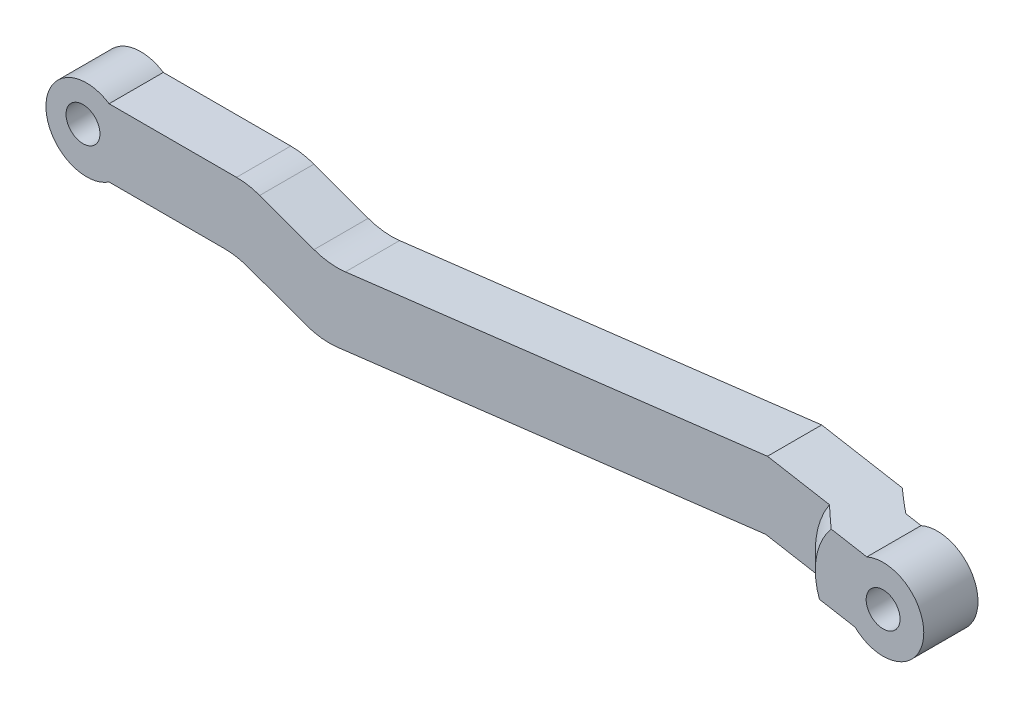
SolidWorks part; units mm, degrees
material "Vero PureWhite"
ref_plane "前视基准面" through (0, 0, 0) normal (0, 0, 1) x (1, 0, 0)
ref_plane "上视基准面" through (0, 0, 0) normal (0, 1, 0) x (1, 0, 0)
ref_plane "右视基准面" through (0, 0, 0) normal (1, 0, 0) x (0, 0, -1)
other "Configuration Table"
sketch "草图1" plane through (0, 0, 0) normal (0, 0, 1) x (1, 0, 0)
  line L0 (0, 0) -> (-120, 0) construction
  line L3 (0, 0) -> (-19.6962, 3.473) construction
  line L4 (-19.6962, 3.473) -> (-84.784, -4.4463) construction
  line L5 (-84.784, -4.4463) -> (-97, 0) construction
  line L6 (-97, 0) -> (-120, 0) construction
  line L7 (-2.398, 5.5) -> (-19.5611, 8.5263)
  line L8 (-19.5611, 8.5263) -> (-84.1992, 0.6618)
  line L9 (-84.1992, 0.6618) -> (-96.1184, 5)
  line L10 (-96.1184, 5) -> (-116.6834, 5)
  line L11 (-4.1345, -4.3481) -> (-19.8313, -1.5803)
  line L12 (-19.8313, -1.5803) -> (-85.3688, -9.5543)
  line L13 (-85.3688, -9.5543) -> (-97.8816, -5)
  line L14 (-97.8816, -5) -> (-116.6834, -5)
  line L15 (0.8682, 4.924) -> (-19.5611, 8.5263) construction
  line L16 (-0.8682, -4.924) -> (-19.8313, -1.5803) construction
  line L17 (-96.1184, 5) -> (-120, 5) construction
  line L18 (-97.8816, -5) -> (-120, -5) construction
  arc A0 (-4.1345, -4.3481) -> (-2.398, 5.5) centre (0, 0) ccw
  arc A1 (-116.6834, 5) -> (-116.6834, -5) centre (-120, 0) ccw
  arc A2 (-0.7041, 5.9585) -> (1.0949, -5.8993) centre (0, 0) ccw construction
  point P3 (-60, 0)
  dimension "D2" = 20
  dimension "D1" = 120
  dimension "D3" = 23
  dimension "D4" = 13
  dimension "D5" = 20
  dimension "D6" = 10
  dimension "D7" = 5
  dimension "D8" = 5
extrude "凸台-拉伸1" add sketch "草图1" along normal mid plane 8
sketch "草图2" plane through (0, 0, -4) normal (0, 0, -1) x (-1, 0, 0)
  circle A0 centre (0, 0) radius 10
  dimension "D1" = 20
extrude "切除-拉伸1" cut sketch "草图2" against normal blind 2.5
sketch "草图3" plane through (0, 0, 4) normal (0, 0, 1) x (1, 0, 0)
  line L2 (-2.398, 5.5) -> (-7.6604, 6.4279)
  line L3 (-9.3969, -3.4202) -> (-4.1345, -4.3481)
  line L4 (-2.398, 5.5) -> (-7.6604, 6.4279)
  line L5 (-9.3969, -3.4202) -> (-4.1345, -4.3481)
  arc A2 (-4.1345, -4.3481) -> (-2.398, 5.5) centre (0, 0) ccw
  arc A3 (-7.6604, 6.4279) -> (-9.3969, -3.4202) centre (0, 0) ccw
  arc A4 (-4.1345, -4.3481) -> (-2.398, 5.5) centre (0, 0) ccw
  arc A5 (-7.6604, 6.4279) -> (-9.3969, -3.4202) centre (0, 0) ccw
  dimension "D1" = 0
extrude "凸台-拉伸4" add sketch "草图3" along normal offset from surface (2.5 mm away) 8 up to face at (-3.9335, 0.6936, -1.5)
sketch "草图4" plane through (0, 0, -1.5) normal (0, 0, -1) x (-1, 0, 0)
  circle A2 centre (0, 0) radius 2.5
  circle A3 centre (120.5349, 0.4793) radius 2.5003
  dimension "D1" = 5
  dimension "D2" = 5.0006
extrude "切除-拉伸2" cut sketch "草图4" against normal through all both and the other way through all
chamfer "倒角1" distance 2.5 angle 45 1 edges at (-9.8481, 1.7365, 4)
chamfer "倒角2" distance 2.5 angle 45 1 edges at (-9.8481, 1.7365, -1.5)
fillet "圆角1" radius 10 4 edges at (-85.3688, -9.5543, 0) (-97.8816, -5, 0) (-84.1992, 0.6618, 0) (-96.1184, 5, 0)
